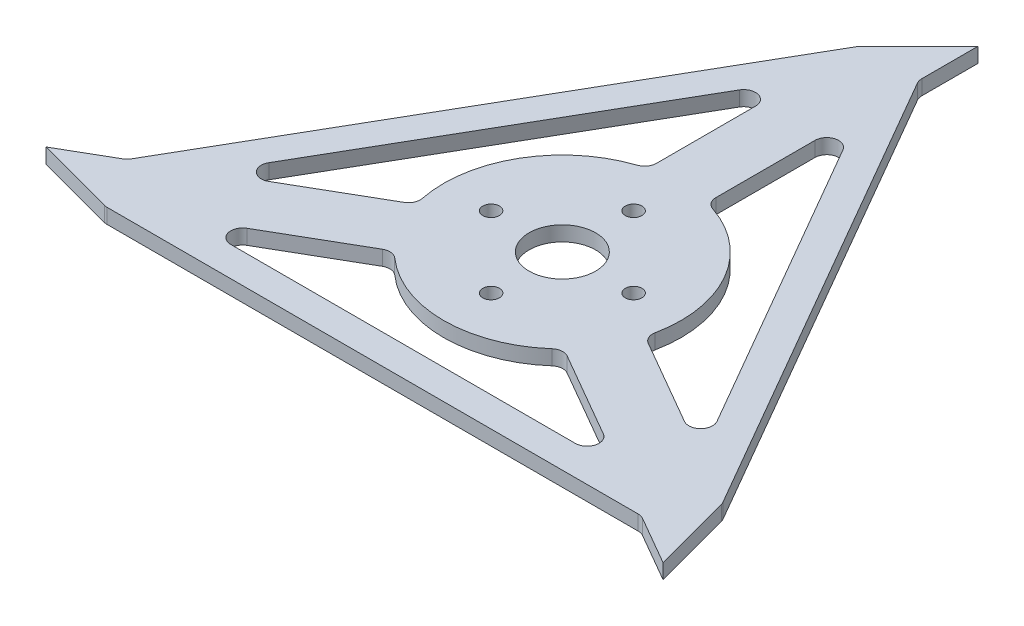
SolidWorks part; units mm, degrees
material "AISI Type A2 Tool Steel"
ref_plane "Front Plane" through (0, 0, 0) normal (0, 0, 1) x (1, 0, 0)
ref_plane "Top Plane" through (0, 0, 0) normal (0, 1, 0) x (1, 0, 0)
ref_plane "Right Plane" through (0, 0, 0) normal (1, 0, 0) x (0, 0, -1)
sketch "Sketch1" plane through (0, 0, 0) normal (0, 1, 0) x (1, 0, 0)
  line L0 (-6.35, 69.85) -> (6.35, 82.55)
  line L1 (63.6669, -29.4257) -> (68.3154, -46.7743)
  line L2 (-6.35, 69.85) -> (-6.35, 0)
  line L3 (-6.35, 0) -> (6.35, 0)
  line L4 (6.35, 82.55) -> (6.35, 0)
  line L5 (-4.6567, 71.5433) -> (6.35, 0) construction
  line L6 (-6.35, 0) -> (6.35, 82.55) construction
  line L7 (68.3154, -46.7743) -> (-3.175, -5.4993)
  line L8 (63.6669, -29.4257) -> (3.175, 5.4993)
  line L9 (3.175, 5.4993) -> (-3.175, -5.4993)
  line L10 (-57.3169, -40.4243) -> (-74.6654, -35.7757)
  line L11 (-74.6654, -35.7757) -> (-3.175, 5.4993)
  line L12 (-57.3169, -40.4243) -> (3.175, -5.4993)
  line L13 (3.175, -5.4993) -> (-3.175, 5.4993)
  line L14 (-57.3169, -40.4243) -> (57.3169, -40.4243)
  line L15 (-46.3184, -34.0743) -> (46.3184, -34.0743)
  line L18 (63.6669, -29.4257) -> (6.35, 69.85)
  line L19 (52.6684, -23.0757) -> (6.35, 57.15)
  line L20 (-63.6669, -29.4257) -> (-6.35, 69.85)
  line L21 (-6.35, 57.15) -> (-52.6684, -23.0757)
  circle A0 centre (0, 0) radius 25.4
  point P3 (0, 41.275)
  point P8 (0, 0)
  point P19 (0, 0)
  point P20 (0, 0)
  point P28 (0, 0)
  point P29 (0, 0)
  point P30 (0, 0)
  dimension "D1" = 50.8
  dimension "D2" = 69.85
  dimension "D3" = 82.55
  dimension "D8" = 6.35
  dimension "D4" = 45
  dimension "D6" = 6.35
  dimension "D5" = 3
  dimension "D7" = 6.35
  dimension "D9" = 12.7
extrude "Boss-Extrude1" add sketch "Sketch1" along normal blind 3.175 contours L1 | A0 L4 L0 L2 | A0 L7 L1 L8 | A0 L11 L10 L12 | L15 L12 L14 L7 | L21 L2 L20 L11 | L19 L8 L18 L4 | L2 A0 L11 | L8 A0 L4 | L12 A0 L7 | L11 A0 L12 L7 L9 L3 L2 | L4 A0 L2 L11 L13 L9 L8 | L7 A0 L8 L4 L3 L13 L12 | L12 L13 L9 L7 | L3 L13 L11 L2 | L8 L9 L3 L4 region at (0.2632, 0, -50.7975) region at (-32.3561, 0, -18.6808) region at (-44.1235, 0, 25.1708) region at (32.3561, 0, -18.6808) region at (0, 0, -14.3487) region at (-15.2402, 0, -8.799) region at (43.8603, 0, 25.6267) region at (-3.7042, 0, -2.1386) region at (-12.4263, 0, 7.1743) region at (15.2402, 0, -8.799) region at (0, 0, 37.3616) region at (12.4263, 0, 7.1743) region at (3.7042, 0, -2.1386) region at (0, 0, 17.5979) region at (0, 0, 4.2772)
sketch "Sketch2" plane through (0, 3.175, 0) normal (0, 1, 0) x (1, 0, 0)
  circle A0 centre (0, 0) radius 7.112
  circle A1 centre (0, 15.24) radius 1.778
  circle A2 centre (15.24, 0) radius 1.778
  circle A3 centre (0, -15.24) radius 1.778
  circle A4 centre (-15.24, 0) radius 1.778
  point P14 (0, 0)
  dimension "D1" = 14.224
  dimension "D2" = 3.556
  dimension "D4" = 4
  dimension "D3" = 15.24
extrude "Cut-Extrude1" cut sketch "Sketch2" against normal through all
fillet "Fillet1" radius 2.54 18 edges at (-24.4735, 1.5875, 6.7975) (-6.35, 1.5875, -24.5934) (6.35, 1.5875, -24.5934) (24.4735, 1.5875, 6.7975) (18.1235, 1.5875, 17.796) (-18.1235, 1.5875, 17.796) (-6.35, 1.5875, -69.85) (-57.3169, 1.5875, 40.4243) (63.6669, 1.5875, 29.4257) (57.3169, 1.5875, 40.4243) (52.6684, 1.5875, 23.0757) (46.3184, 1.5875, 34.0743) (-63.6669, 1.5875, 29.4257) (-52.6684, 1.5875, 23.0757) (-46.3184, 1.5875, 34.0743) (6.35, 1.5875, -69.85) (6.35, 1.5875, -57.15) (-6.35, 1.5875, -57.15)
